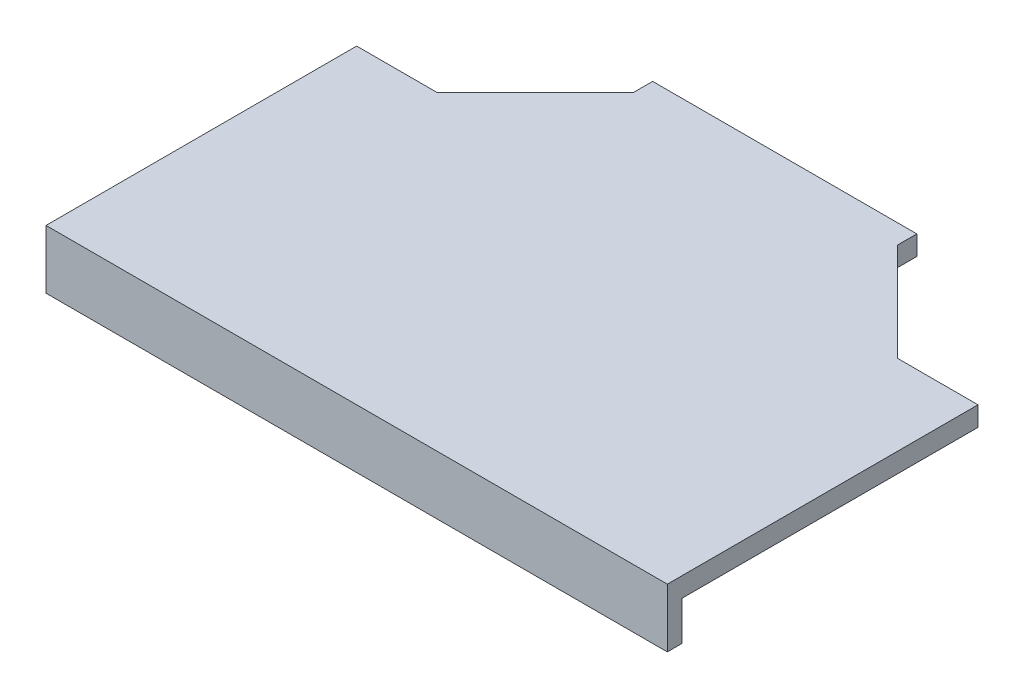
SolidWorks part; units mm, degrees
ref_plane "Front Plane" through (0, 0, 0) normal (0, 0, 1) x (1, 0, 0)
ref_plane "Top Plane" through (0, 0, 0) normal (0, 1, 0) x (1, 0, 0)
ref_plane "Right Plane" through (0, 0, 0) normal (1, 0, 0) x (0, 0, -1)
sketch "Sketch1" plane through (0, 0, 0) normal (0, 0, 1) x (1, 0, 0)
  line L1 (13.5, 5.4) -> (-13.5, 5.4)
  line L2 (13.5, 5.4) -> (13.5, -5.4)
  line L3 (13.5, -5.4) -> (-13.5, -5.4)
  line L4 (-13.5, 5.4) -> (-13.5, -5.4)
  line L5 (13.5, 5.4) -> (-13.5, -5.4) construction
  line L6 (13.5, -5.4) -> (-13.5, 5.4) construction
  point P0 (0, 0)
extrude "Boss-Extrude1" add sketch "Sketch1" along normal blind 2
sketch "Sketch2" plane through (0, 5.4, 0) normal (0, 1, 0) x (1, 0, 0)
  line L5 (0, 12) -> (-13.5, 12) construction
  line L6 (0, 12) -> (5.94, 12) construction
  line L7 (-13.5, -2) -> (-13.5, 12) construction
  line L9 (13.5, -2) -> (-13.5, -2)
  line L10 (13.5, -2) -> (13.5, 12)
  line L11 (13.5, 12) -> (-13.5, 12)
  line L12 (-13.5, -2) -> (-13.5, 12)
extrude "Boss-Extrude2" add sketch "Sketch2" along normal blind 2
sketch "Sketch4" plane through (0, 0, 2) normal (0, 0, 1) x (1, 0, 0)
  line L1 (-13.5, -5.4) -> (13.5, -5.4)
  line L2 (-13.5, -5.4) -> (-13.5, 7.4)
  line L3 (-13.5, 7.4) -> (13.5, 7.4)
  line L4 (13.5, -5.4) -> (13.5, 7.4)
extrude "Boss-Extrude3" add sketch "Sketch4" along normal blind 4
sketch "Sketch6" plane through (0, 0, 6) normal (0, 0, 1) x (1, 0, 0)
  line L1 (13.5, -5.4) -> (2.3261, -5.4)
  line L2 (13.5, -5.4) -> (13.5, -1.1266)
  line L3 (13.5, -1.1266) -> (2.3261, -1.1266)
  line L4 (2.3261, -5.4) -> (2.3261, -1.1266)
extrude "Cut-Extrude1" cut sketch "Sketch6" against normal through all
sketch "Sketch7" plane through (0, 0, 0) normal (0, 0, -1) x (-1, 0, 0)
  circle A0 centre (11.7, -3.3) radius 1.05
  circle A1 centre (-11.7, 3.3) radius 1.05
  dimension "D1" = 2.1
  dimension "D2" = 2.1
extrude "Cut-Extrude2" cut sketch "Sketch7" against normal through all
sketch "Sketch8" plane through (0, 0, 6) normal (0, 0, 1) x (1, 0, 0)
  line L1 (13.5, -1.1266) -> (9.2795, -1.1266)
  line L2 (13.5, -1.1266) -> (13.5, 5.5636)
  line L3 (13.5, 5.5636) -> (9.2795, 5.5636)
  line L4 (9.2795, -1.1266) -> (9.2795, 5.5636)
extrude "Cut-Extrude3" cut sketch "Sketch8" against normal offset from surface (4 mm away) 2 up to face at (-12.75, -3.3, 0)
sketch "Sketch9" plane through (0, 0, 6) normal (0, 0, 1) x (1, 0, 0)
  line L1 (-13.5, -5.4) -> (-8.6985, -5.4)
  line L2 (-13.5, -5.4) -> (-13.5, -0.256)
  line L3 (-13.5, -0.256) -> (-8.6985, -0.256)
  line L4 (-8.6985, -5.4) -> (-8.6985, -0.256)
extrude "Cut-Extrude4" cut sketch "Sketch9" against normal offset from surface (4 mm away) 2 up to face at (-12.75, -3.3, 0)
sketch "Sketch10" plane through (0, 7.4, 0) normal (0, 1, 0) x (1, 0, 0)
  line L0 (-31.75, -31.75) -> (31.75, -31.75)
  line L2 (31.75, -31.75) -> (31.75, 0)
  line L3 (31.75, 0) -> (-31.75, 0)
  line L4 (-31.75, 0) -> (-31.75, -31.75)
  point P3 (0, -31.75)
  point P6 (0, 0)
  dimension "D1" = 63.5
  dimension "D2" = 31.75
extrude "Boss-Extrude5" add sketch "Sketch10" against normal up to surface (2 mm away) up to face at (0, 5.4, -6)
sketch "Sketch11" plane through (0, 0, 2) normal (0, 0, 1) x (1, 0, 0)
  line L0 (9.2795, -1.1266) -> (2.3261, -1.1266) construction
  line L1 (9.2795, 5.4) -> (6.6218, 5.4)
  line L2 (9.2795, 5.4) -> (9.2795, -1.1266)
  line L3 (9.2795, -1.1266) -> (6.6218, -1.1266)
  line L4 (6.6218, 5.4) -> (6.6218, -1.1266)
  circle A0 centre (-13.5, -5.4) radius 7.0367
extrude "Cut-Extrude5" cut sketch "Sketch11" along normal up to surface (4 mm away) up to face at (-2.6482, -0.3457, 6)
chamfer "Chamfer1" distance 10 angle 45 2 edges at (-13.5, 6.4, 0) (13.5, 6.4, 0)
sketch "Sketch12" plane through (0, 5.4, 0) normal (0, -1, 0) x (1, 0, 0)
  line L0 (31.75, 0) -> (31.75, 31.75) construction
  line L1 (-31.75, 31.75) -> (31.75, 31.75)
  line L2 (-31.75, 31.75) -> (-31.75, 30.25)
  line L3 (-31.75, 30.25) -> (31.75, 30.25)
  line L4 (31.75, 31.75) -> (31.75, 30.25)
  dimension "D1" = 1.5
extrude "Boss-Extrude6" add sketch "Sketch12" along normal blind 4
